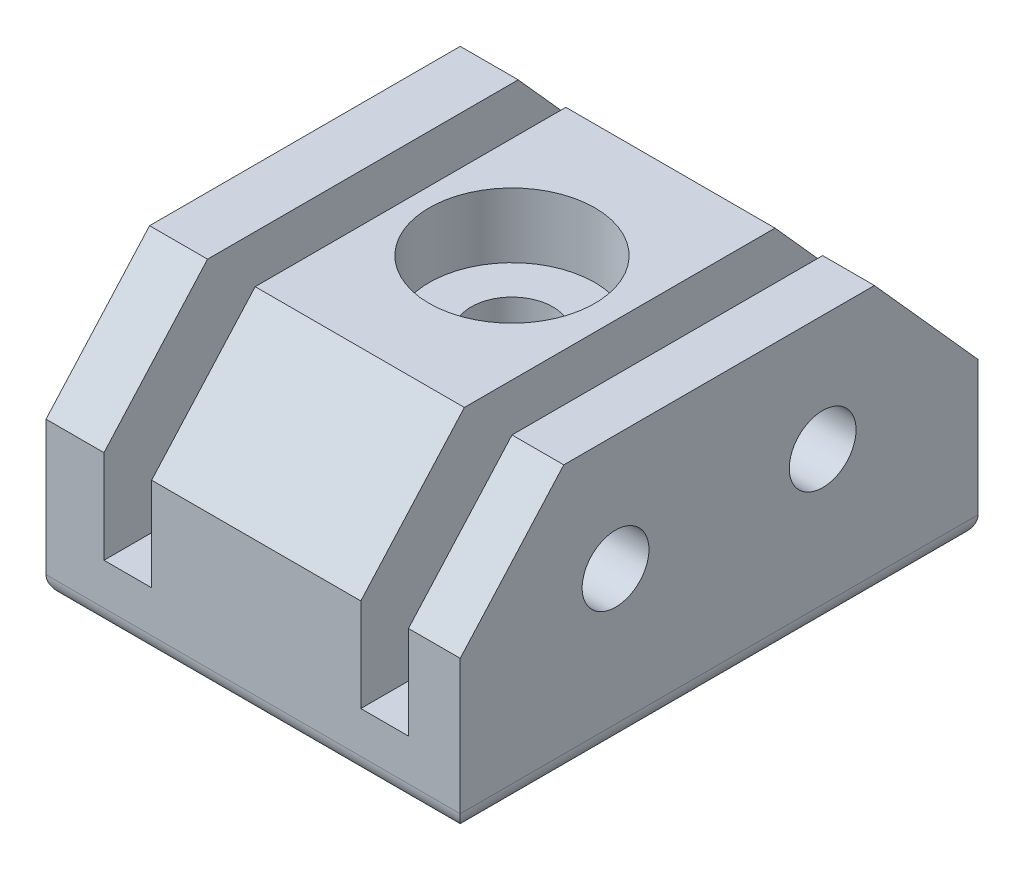
SolidWorks part; units mm, degrees
ref_plane "Front Plane" through (0, 0, 0) normal (0, 0, 1) x (1, 0, 0)
ref_plane "Top Plane" through (0, 0, 0) normal (0, 1, 0) x (1, 0, 0)
ref_plane "Right Plane" through (0, 0, 0) normal (1, 0, 0) x (0, 0, -1)
sketch "Sketch1" plane through (0, 0, 0) normal (1, 0, 0) x (0, 0, -1)
  line L1 (0, 0) -> (63.5, 0)
  line L2 (0, 0) -> (0, 6.35)
  line L3 (0, 6.35) -> (63.5, 6.35)
  line L4 (63.5, 0) -> (63.5, 6.35)
  dimension "D1" = 6.35
  dimension "D2" = 63.5
extrude "Boss-Extrude1" add sketch "Sketch1" against normal blind 50.8
sketch "Sketch2" plane through (0, 0, 0) normal (1, 0, 0) x (0, 0, -1)
  line L0 (0, 6.35) -> (0, 19.05)
  line L1 (0, 19.05) -> (12.7, 33.249)
  line L2 (12.7, 33.249) -> (50.8, 33.249)
  line L3 (50.8, 33.249) -> (63.5, 19.05)
  line L4 (63.5, 19.05) -> (63.5, 6.35)
  line L5 (63.5, 6.35) -> (0, 6.35)
  point P7 (31.75, 33.249)
  point P10 (31.75, 6.35)
  dimension "D1" = 38.1
  dimension "D2" = 12.7
  dimension "D3" = 12.7
  dimension "D4" = 19.05
  dimension "D5" = 19.05
extrude "Boss-Extrude2" add sketch "Sketch2" against normal blind 50.8
sketch "Sketch10" plane through (0, 0, -63.5) normal (0, 0, -1) x (-1, 0, 0)
  line L1 (50.8, 33.249) -> (0, 33.249) construction
  line L3 (6.35, 7.62) -> (6.35, 33.249)
  line L4 (6.35, 33.249) -> (12.192, 33.249)
  line L5 (12.192, 7.62) -> (12.192, 33.249)
  line L6 (6.35, 7.62) -> (12.192, 7.62)
  line L8 (50.8, 0) -> (0, 0) construction
  point P11 (12.192, 7.62)
  dimension "D1" = 7.62
  dimension "D2" = 5.842
  dimension "D3" = 6.35
extrude "Cut-Extrude1" cut sketch "Sketch10" against normal through all
pattern_linear "LPattern3" count 2 spacing 31.496 along (-1, 0, 0) of "Cut-Extrude1"
sketch "Sketch11" plane through (0, 0, 0) normal (1, 0, 0) x (0, 0, -1)
  circle A0 centre (19.05, 19.05) radius 4.0957
  circle A1 centre (19.05, 19.05) radius 7.9375 construction
  circle A2 centre (44.45, 19.05) radius 4.0958
  circle A3 centre (44.45, 19.05) radius 7.9375 construction
  dimension "D1" = 8.1915
  dimension "D3" = 15.875
  dimension "D4" = 8.1915
  dimension "D6" = 15.875
  dimension "D2" = 6.35
  dimension "D5" = 6.35
extrude "Cut-Extrude2" cut sketch "Sketch11" against normal through all
sketch "Sketch14" plane through (0, 33.249, 0) normal (0, 1, 0) x (1, 0, 0)
  line L3 (-37.846, 12.7) -> (-37.846, 50.8) construction
  point P0 (-25.4, 31.75)
  point P4 (-37.846, 31.75)
  dimension "D1" = 12.446
sketch "Sketch17" plane through (0, 40.0201, -44.7438) normal (0, 0.6667, -0.7454) x (-1, 0, 0)
  line L0 (12.192, -28.1343) -> (12.192, -9.0843) construction
  line L1 (37.846, -9.0843) -> (12.192, -9.0843) construction
  point P0 (25.019, -18.6093)
  point P4 (12.192, -18.6093)
  point P7 (25.019, -9.0843)
sketch "Sketch18" plane through (0, 8.4667, 9.466) normal (0, 0.6667, 0.7454) x (1, 0, 0)
  line L0 (-12.192, 33.249) -> (-12.192, 14.199) construction
  line L1 (-37.846, 33.249) -> (-12.192, 33.249) construction
  point P0 (-25.019, 23.724)
  point P1 (-25.019, 23.724)
  point P4 (-12.192, 23.724)
  point P7 (-25.019, 33.249)
ref_plane "Plane2" through (0, 33.02, 0) normal (0, -1, 0) x (-1, 0, 0)
fillet "Fillet1" radius 2.54 4 edges at (0, 0, -31.75) (-50.8, 0, -31.75) (-25.4, 0, 0) (-25.4, 0, -63.5)
sketch "Sketch22" plane through (0, 33.249, 0) normal (0, -1, 0) x (1, 0, 0)
  line L1 (-25.4, -63.5) -> (-25.4, 0) construction
  line L2 (-50.8, -63.5) -> (0, -63.5) construction
  line L3 (-50.8, 0) -> (0, 0) construction
  line L4 (0, -31.75) -> (-50.8, -31.75) construction
  line L6 (0, 0) -> (0, -63.5) construction
  line L7 (-50.8, 0) -> (-50.8, -63.5) construction
  circle A1 centre (-25.4, -31.75) radius 10.16
  dimension "D1" = 20.32
extrude "Cut-Extrude8" cut sketch "Sketch22" along normal blind 7.9375
sketch "Sketch24" plane through (0, 0, 0) normal (0, -1, 0) x (1, 0, 0)
  line L0 (-25.4, -63.5) -> (-25.4, 0) construction
  line L1 (-50.8, -63.5) -> (0, -63.5) construction
  line L2 (-50.8, 0) -> (0, 0) construction
  line L3 (0, -31.75) -> (-50.8, -31.75) construction
  line L4 (0, 0) -> (0, -63.5) construction
  line L5 (-50.8, 0) -> (-50.8, -63.5) construction
  circle A0 centre (-25.4, -31.75) radius 5
  dimension "D1" = 10
extrude "Cut-Extrude10" cut sketch "Sketch24" against normal through all
sketch "Sketch25" plane through (0, 0, 0) normal (0, -1, 0) x (1, 0, 0)
  circle A0 centre (-25.4, -31.75) radius 10.16
  dimension "D1" = 20.32
extrude "Cut-Extrude11" cut sketch "Sketch25" against normal blind 2.54
